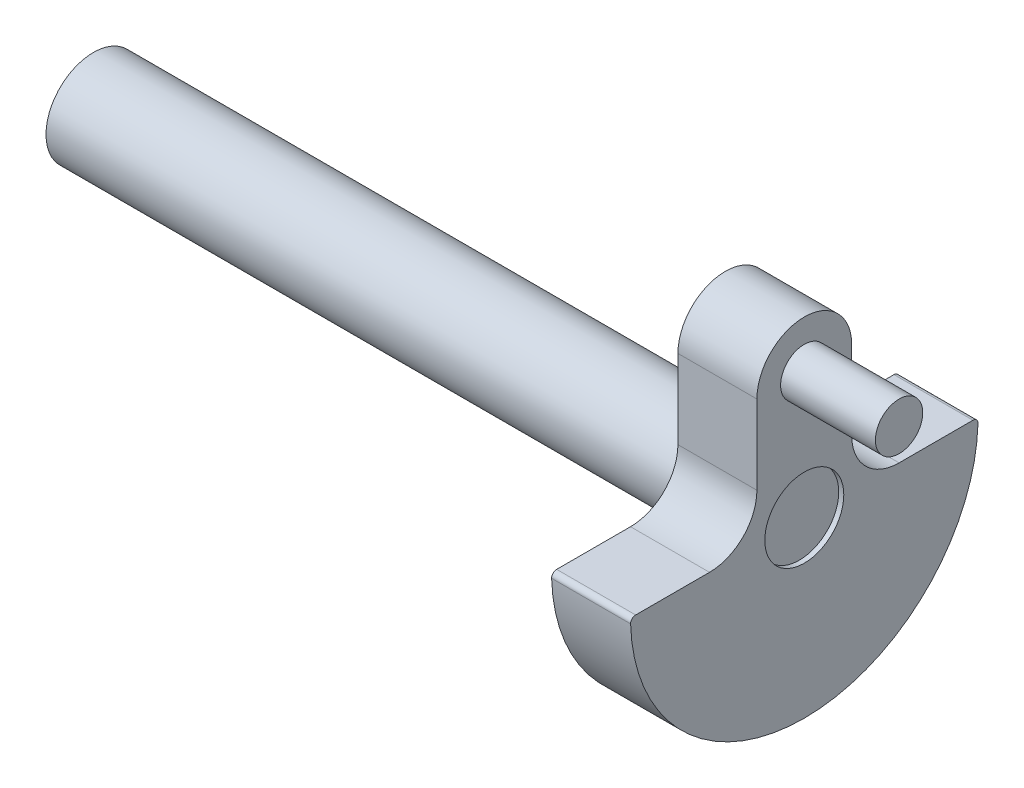
SolidWorks part; units mm, degrees
ref_plane "Front Plane" through (0, 0, 0) normal (0, 0, 1) x (1, 0, 0)
ref_plane "Top Plane" through (0, 0, 0) normal (0, 1, 0) x (1, 0, 0)
ref_plane "Right Plane" through (0, 0, 0) normal (1, 0, 0) x (0, 0, -1)
sketch "Sketch3" plane through (0, 0, 0) normal (1, 0, 0) x (0, 0, -1)
  line L0 (-14.1255, 0) -> (0, 0) construction
  line L1 (0, 12.3916) -> (0, -12.1689) construction
  line L2 (-2.3812, 6.35) -> (-2.3812, 2.3813)
  line L3 (2.3813, 6.35) -> (2.3813, 2.3813)
  line L4 (-8.4734, 0) -> (-4.7625, 0)
  line L5 (4.7625, 0) -> (8.4734, 0)
  line L6 (2.3813, 0) -> (14.9845, 0) construction
  arc A0 (-8.7273, -0.2616) -> (8.7273, -0.2616) centre (0, 0) ccw
  arc A1 (2.3813, 6.35) -> (-2.3812, 6.35) centre (0, 6.35) ccw
  arc A2 (-8.7273, -0.2616) -> (-8.4734, 0) centre (-8.4734, -0.254) cw
  arc A3 (8.4734, 0) -> (8.7273, -0.2616) centre (8.4734, -0.254) cw
  arc A4 (4.7625, 0) -> (2.3813, 2.3813) centre (4.7625, 2.3812) cw
  arc A5 (-2.3812, 2.3813) -> (-4.7625, 0) centre (-4.7625, 2.3813) cw
  point P15 (-8.7312, 0)
  point P18 (8.7312, 0)
  point P24 (-2.3812, 0)
  dimension "D1" = 17.4625
  dimension "D2" = 4.7625
  dimension "D4" = 0.254
  dimension "D5" = 0.254
  dimension "D6" = 2.3813
  dimension "D3" = 6.35
extrude "Boss-Extrude1" add sketch "Sketch3" along normal blind 3.9688
sketch "Sketch4" plane through (0, 0, 0) normal (-1, 0, 0) x (0, 0, 1)
  circle A0 centre (0, 6.35) radius 1.1906
  circle A1 centre (0, 0) radius 2.3813
  dimension "D1" = 2.3813
  dimension "D2" = 4.7625
extrude "Boss-Extrude2" add sketch "Sketch4" along normal blind 31.75 contours A1 region at (0, 0, 0)
extrude "Boss-Extrude3" add sketch "Sketch4<3>" against normal blind 8.7312 contours A0 region at (0, 6.35, 0)
sketch "Sketch4<3>" plane through (0, 0, 0) normal (-1, 0, 0) x (0, 0, 1) same geometry as "Sketch4"
sketch "Sketch5" plane through (3.9688, 0, 0) normal (1, 0, 0) x (0, 0, -1)
  circle A0 centre (0, 0) radius 1.9844
  dimension "D1" = 3.9688
extrude "Cut-Extrude1" cut sketch "Sketch5" against normal blind 0.254
